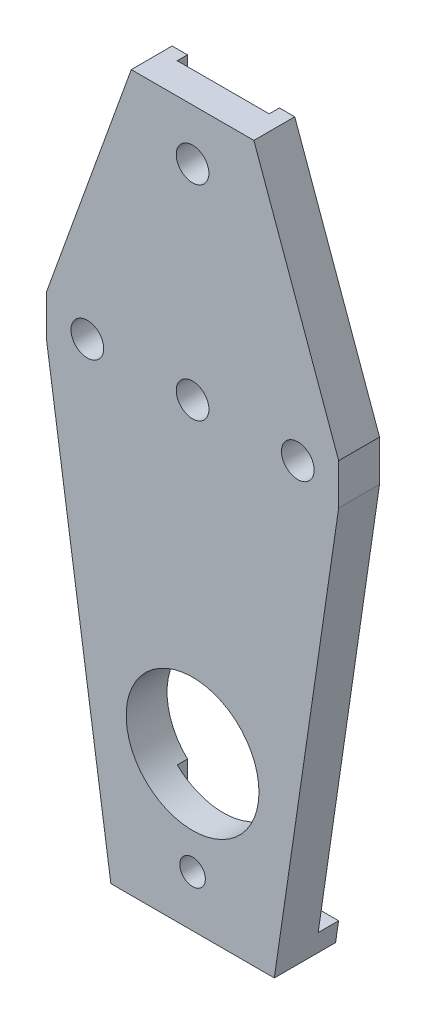
SolidWorks part; units mm, degrees
material "7075-O (SS)"
ref_plane "前视基准面" through (0, 0, 0) normal (0, 0, 1) x (1, 0, 0)
ref_plane "上视基准面" through (0, 0, 0) normal (0, 1, 0) x (1, 0, 0)
ref_plane "右视基准面" through (0, 0, 0) normal (1, 0, 0) x (0, 0, -1)
sketch "Model" plane through (0, 0, 0) normal (0, 0, 1) x (1, 0, 0)
  line L0 (29.5406, 32.4545) -> (37.8406, 9.4545)
  line L2 (37.8406, 5.4545) -> (37.8406, 9.4545)
  line L3 (31.5406, -37.5455) -> (37.8406, 5.4545)
  line L4 (28.0406, -35.5455) -> (31.8336, -35.5455)
  line L5 (28.0406, -37.5455) -> (28.0406, -27.2359)
  line L6 (28.0406, -17.855) -> (28.0406, 32.4545)
  line L7 (19.0406, -17.855) -> (19.0406, 32.4545)
  line L8 (19.0406, -37.5455) -> (19.0406, -27.2359)
  line L9 (15.5406, -37.5455) -> (9.2406, 5.4545)
  line L10 (9.2406, 5.4545) -> (9.2406, 9.4545)
  line L11 (17.5406, 32.4545) -> (9.2406, 9.4545)
  line L12 (17.5406, 32.4545) -> (29.5406, 32.4545)
  line L13 (31.5406, -37.5455) -> (15.5406, -37.5455)
  line L14 (19.0406, -35.5455) -> (15.2476, -35.5455)
  circle A0 centre (33.8406, 7.4545) radius 3.245
  circle A4 centre (23.5406, 27.4545) radius 1.6
  circle A5 centre (23.5406, 7.4545) radius 1.6
  circle A6 centre (13.2406, 7.4545) radius 3.245
  circle A7 centre (23.5406, -22.5455) radius 6.5
  circle A8 centre (13.2406, 7.4545) radius 1.6
  circle A9 centre (33.8406, 7.4545) radius 1.6
extrude "凸台-拉伸4" add sketch "Model" against normal blind 4 contours A7 L7 L12 L11 L10 L9 L14 L8 A6 | A7 L5 L4 L3 L2 L12 L6 A0 | A0 A9 | L13 L3 L4 L5 | L8 L14 L9 L13 | A8 | A6 region at (31.6033, -1.6335, 0) region at (15.4779, -1.6335, 0) region at (29.8648, -36.5321, 0) region at (17.2164, -36.5321, 0) region at (30.6874, 7.4545, 0) region at (13.2406, 7.4545, 0)
extrude "凸台-拉伸5" add sketch "Model<7>" against normal blind 3 contours A7 L8 L13 L5 | A7 L6 L12 L7 A4 A5 region at (27.5295, 7.2998, 0) region at (23.5406, -32.9977, 0)
sketch "Model<7>" plane through (0, 0, 0) normal (0, 0, 1) x (1, 0, 0) same geometry as "Model"
extrude "凸台-拉伸6" add sketch "Model<8>" against normal blind 6 contours L13 L3 L4 L5 | L8 L14 L9 L13 region at (29.8648, -36.5321, 0) region at (17.2164, -36.5321, 0)
sketch "Model<8>" plane through (0, 0, 0) normal (0, 0, 1) x (1, 0, 0) same geometry as "Model"
chamfer "倒角2" distance 1.65 angle 45 2 edges at (14.8406, 7.4545, -4) (35.4406, 7.4545, -4)
sketch "草图1" plane through (0, 0, -3) normal (0, 0, -1) x (-1, 0, 0)
  line L0 (-23.5406, 32.4545) -> (-23.5406, -37.5455) construction
  line L1 (-19.0406, 32.4545) -> (-28.0406, 32.4545) construction
  line L2 (-28.0406, -37.5455) -> (-19.0406, -37.5455) construction
  circle A0 centre (-23.5406, -32.5455) radius 1.2494
  dimension "D1" = 5
  dimension "D2" = 2.4989
extrude "切除-拉伸1" cut sketch "草图1" against normal blind 10
hole_wizard "M3 螺纹孔2" positions "3D草图2" profile "草图3" tap size "M3" standard "GB" end condition through all
sketch3d "3D草图2"
  line L0 (23.5406, -32.5455, 0) -> (23.5406, -32.5455, -3) construction
  point P0 (23.5406, -32.5455, -3)
sketch "草图3" plane through (23.5406, -32.5455, -3) normal (1, 0, 0) x (0, 1, 0)
  line L0 (0, 0) -> (0, 3)
  line L1 (0, 3) -> (1.25, 3)
  line L2 (1.25, 3) -> (1.25, 0.275)
  line L3 (1.25, 0.275) -> (1.525, 0)
  line L5 (1.525, 0) -> (0, 0)
  line L6 (-1.25, 0.275) -> (-1.525, 0) construction
  line L11 (0, -6.35) -> (0, 107.95) construction
  dimension "通孔螺纹孔钻头直径" = 2.5
  dimension "通孔螺纹孔钻头深度" = 3
  dimension "近端锥形沉头孔直径" = 3.05
  dimension "近端锥形沉头孔角度" = 90
cosmetic thread "孔螺蚊线3" parameters "D2"=3
